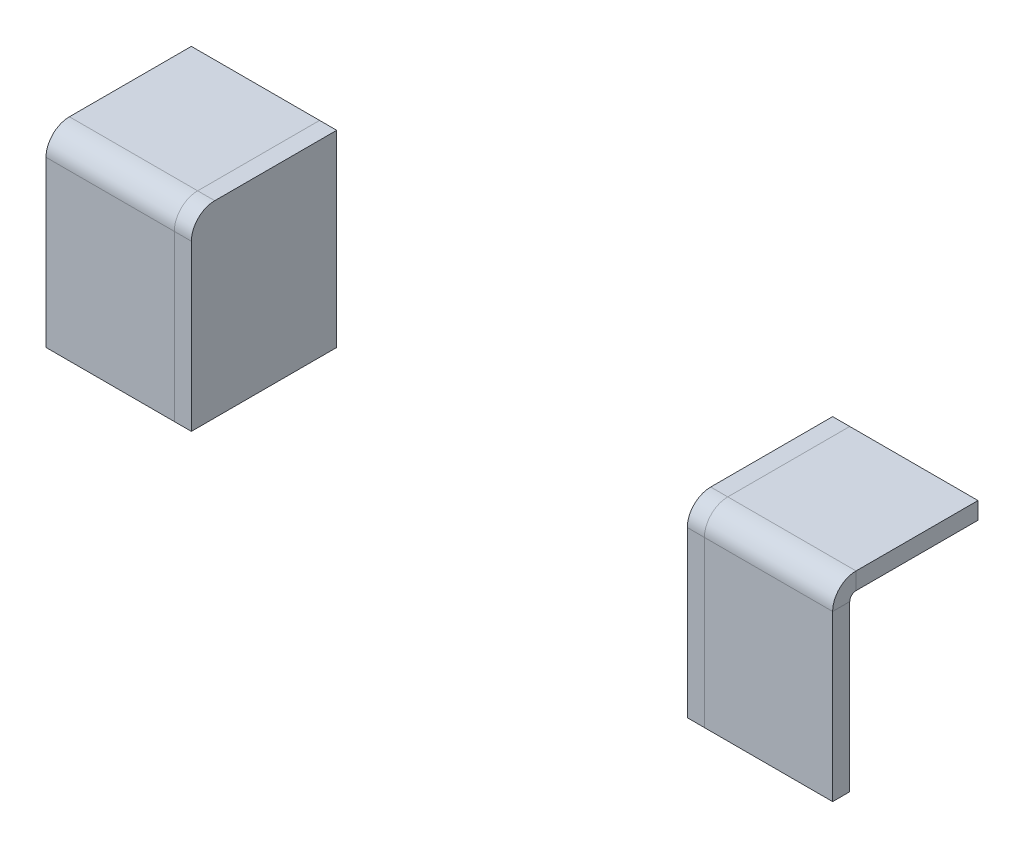
SolidWorks part; units mm, degrees
note: The reader was unsure of these and kept them because the rebuilt part matched: flange length of "Edge-Flange1".
ref_plane "Front Plane" through (0, 0, 0) normal (0, 0, 1) x (1, 0, 0)
ref_plane "Top Plane" through (0, 0, 0) normal (0, 1, 0) x (1, 0, 0)
ref_plane "Right Plane" through (0, 0, 0) normal (1, 0, 0) x (0, 0, -1)
sketch "Sketch1" plane through (0, 0, 0) normal (0, 1, 0) x (1, 0, 0)
  line L1 (-7.5, -8.5) -> (7.5, -8.5)
  line L2 (-7.5, -8.5) -> (-7.5, 8.5)
  line L3 (-7.5, 8.5) -> (7.5, 8.5)
  line L4 (7.5, -8.5) -> (7.5, 8.5)
  line L5 (-7.5, -8.5) -> (7.5, 8.5) construction
  line L6 (-7.5, 8.5) -> (7.5, -8.5) construction
  point P0 (0, 0)
  dimension "D1" = 17
  dimension "D2" = 15
base flange "Base-Flange1" sketch "Sketch1" thickness 2 reverse thickness direction no parameters "D1"=0.7366
edge flange "Edge-Flange1" sketch "Sketch8" flange angle 90 flange length 20 flange position material inside bend radius 0.7366 thickness 2 relief rectangular parameters "D6"=10
sketch "Sketch8" plane through (0, -2, 8.5) normal (0, 0, 1) x (-1, 0, 0)
  line L0 (7.5, 0) -> (-7.5, 0) construction
  line L1 (7.5, 0) -> (-7.5, 0)
  line L2 (-7.5, 0) -> (-7.5, 20)
  line L3 (-7.5, 20) -> (7.5, 20)
  line L4 (7.5, 20) -> (7.5, 0)
bend "EdgeBend1" bend radius 0.7366 bend angle 90 parameters "D5"=1
sketch "Sketch9" plane through (7.5, 0, 0) normal (1, 0, 0) x (0, 0, -1)
  line L0 (-8.5, -22) -> (-8.5, -2.7366) construction
  line L1 (-5.7634, 0) -> (8.5, 0) construction
  line L2 (-8.5, -22) -> (-8.5, -2.7366)
  line L3 (-5.7634, 0) -> (8.5, 0)
  line L4 (-8.5, -22) -> (8.5, -22)
  line L5 (8.5, -22) -> (8.5, 0)
  arc A0 (-5.7634, 0) -> (-8.5, -2.7366) centre (-5.7634, -2.7366) ccw construction
  arc A1 (-5.7634, 0) -> (-8.5, -2.7366) centre (-5.7634, -2.7366) ccw
base flange "Base-Flange2" sketch "Sketch9" thickness 2 reverse thickness direction yes parameters "D1"=0.7366
ref_plane "Plane1" through (38.5, 0, 0) normal (-1, 0, 0) x (0, 0, 1)
mirror "Mirror1" about plane through (38.5, 0, 0) normal (-1, 0, 0) of bodies 102 103
bend "DerivedBend1" bend radius 0.7366 bend angle 90 parameters "D5"=1
sketch "Bend-Lines1" [suppressed] plane through (0, 0, 0) normal (0, 1, 0) x (1, 0, 0)
sketch "Bounding-Box1" [suppressed] plane through (0, 0, 0) normal (0, 1, 0) x (1, 0, 0)
sheet metal parameters "Sheet-Metal1" thickness 2 parameters "D1"=0.7366
flat pattern "Flat-Pattern1" [suppressed]
sketch "Bend-Lines2" plane through (0, 0, 0) normal (0, 1, 0) x (1, 0, 0)
sketch3d "Bounding-Box2" [suppressed]
  line L0 (-46, 13, 0) -> (46, 13, 0) construction
  line L1 (-46, -13, 0) -> (46, -13, 0) construction
  line L2 (-46, 13, 0) -> (-46, -13, 0) construction
  line L3 (46, 13, 0) -> (46, -13, 0) construction
sheet metal parameters "Sheet-Metal2" thickness 2 parameters "D1"=0.7366
flat pattern "Flat-Pattern1"
sketch "Bend-Lines2" plane through (0, 0, 0) normal (0, 1, 0) x (1, 0, 0)
  line L0 (-7.5, -5.9634) -> (7.5, -5.9634) construction
  line L1 (-7.5, -5.9634) -> (7.5, -5.9634) construction
sketch3d "Bounding-Box2" [suppressed]
  line L0 (-7.5, -25.4268, 0) -> (-7.5, 8.5, 0) construction
  line L1 (7.5, -25.4268, 0) -> (7.5, 8.5, 0) construction
  line L2 (-7.5, -25.4268, 0) -> (7.5, -25.4268, 0) construction
  line L3 (-7.5, 8.5, 0) -> (7.5, 8.5, 0) construction
bend of the flat pattern "Flatten-<EdgeBend1>1"
sheet metal parameters "Sheet-Metal3" thickness 2 parameters "D1"=0.7366
flat pattern "Flat-Pattern3"
sketch "Bend-Lines3" plane through (0, 0, 0) normal (0, 1, 0) x (1, 0, 0)
sketch3d "Bounding-Box3" [suppressed]
  line L0 (-14.2634, 2.7366, 0) -> (-14.2634, -19.2634, 0) construction
  line L1 (2.7366, 2.7366, 0) -> (2.7366, -19.2634, 0) construction
  line L2 (-14.2634, 2.7366, 0) -> (2.7366, 2.7366, 0) construction
  line L3 (-14.2634, -19.2634, 0) -> (2.7366, -19.2634, 0) construction
sheet metal parameters "Sheet-Metal4" thickness 2 parameters "D1"=0.7366
flat pattern "Flat-Pattern4" [suppressed]
sketch "Bend-Lines4" plane through (0, 0, 0) normal (0, 1, 0) x (1, 0, 0)
sketch "Bounding-Box4" [suppressed] plane through (0, 0, 0) normal (0, 1, 0) x (1, 0, 0)
bend of the flat pattern "Flatten-<DerivedBend1>1"
sheet metal parameters "Sheet-Metal5" thickness 2 parameters "D1"=0.7366
flat pattern "Flat-Pattern5"
sketch "Bend-Lines5" plane through (0, 0, 0) normal (0, 1, 0) x (1, 0, 0)
sketch "Bounding-Box5" [suppressed] plane through (0, 0, 0) normal (0, 1, 0) x (1, 0, 0)
